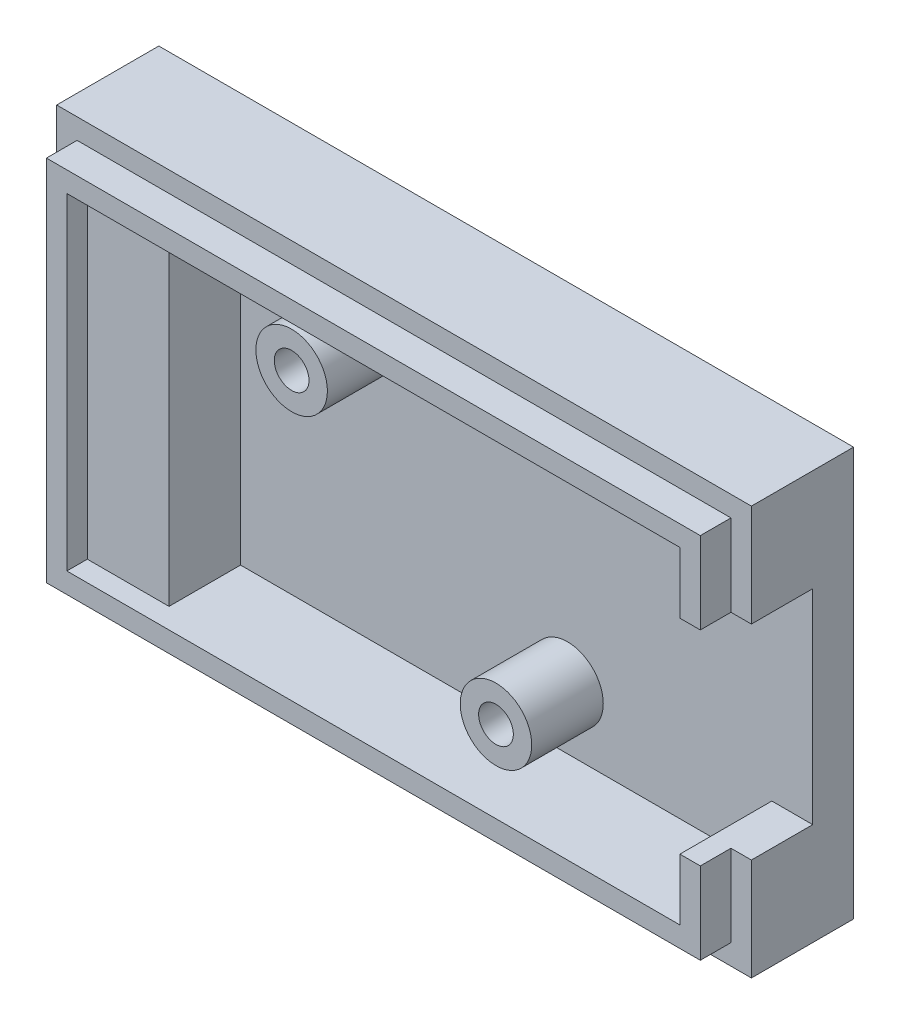
SolidWorks part; units mm, degrees
ref_plane "前视基准面" through (0, 0, 0) normal (0, 0, 1) x (1, 0, 0)
ref_plane "上视基准面" through (0, 0, 0) normal (0, 1, 0) x (1, 0, 0)
ref_plane "右视基准面" through (0, 0, 0) normal (1, 0, 0) x (0, 0, -1)
sketch "草图1" plane through (0, 0, 0) normal (0, 0, 1) x (1, 0, 0)
  line L1 (-17, 10) -> (17, 10)
  line L2 (-17, 10) -> (-17, -10)
  line L3 (-17, -10) -> (17, -10)
  line L4 (17, 10) -> (17, -10)
  line L5 (-17, 10) -> (17, -10) construction
  line L6 (-17, -10) -> (17, 10) construction
  point P0 (0, 0)
  dimension "D1" = 20
  dimension "D2" = 34
extrude "凸台-拉伸1" add sketch "草图1" along normal blind 6.5
sketch "草图2" plane through (0, 0, 6.5) normal (0, 0, 1) x (1, 0, 0)
  line L0 (17, -10) -> (17, 10) construction
  line L1 (-15, 8) -> (15, 8)
  line L2 (-15, 8) -> (-15, -8)
  line L3 (-15, -8) -> (15, -8)
  line L4 (15, 8) -> (15, -8)
  line L5 (-15, 8) -> (15, -8) construction
  line L6 (-15, -8) -> (15, 8) construction
  line L7 (17, 10) -> (-17, 10) construction
  point P0 (0, 0)
  dimension "D1" = 2
  dimension "D2" = 2
extrude "切除-拉伸1" cut sketch "草图2" against normal blind 4.5
sketch "草图3" plane through (17, 0, 0) normal (1, 0, 0) x (0, 0, -1)
  line L0 (-6.5, -10) -> (-6.5, 10) construction
  line L1 (-6.5, 5) -> (-2, 5)
  line L2 (-6.5, 5) -> (-6.5, -5)
  line L3 (-6.5, -5) -> (-2, -5)
  line L4 (-2, 5) -> (-2, -5)
  line L5 (-6.5, 10) -> (0, 10) construction
  line L6 (-6.5, -10) -> (0, -10) construction
  dimension "D1" = 5
  dimension "D2" = 5
  dimension "D3" = 4.5
extrude "切除-拉伸2" cut sketch "草图3" against normal blind 2
sketch "草图4" plane through (0, 0, 6.5) normal (0, 0, 1) x (1, 0, 0)
  line L0 (16, 5) -> (16, 9)
  line L1 (15, 5) -> (17, 5) construction
  line L2 (16, 9) -> (-16, 9)
  line L3 (-16, 9) -> (-16, -9)
  line L4 (-16, -9) -> (16, -9)
  line L5 (16, -9) -> (16, -5)
  line L6 (15, -5) -> (17, -5) construction
  line L7 (16, -5) -> (17, -5)
  line L8 (17, -5) -> (17, -10)
  line L9 (17, -10) -> (-17, -10)
  line L10 (-17, -10) -> (-17, 10)
  line L11 (-17, 10) -> (17, 10)
  line L12 (17, 10) -> (17, 5)
  line L13 (17, 5) -> (16, 5)
  dimension "D1" = 1
  dimension "D2" = 1
  dimension "D3" = 1
extrude "切除-拉伸3" cut sketch "草图4" against normal blind 1.5
sketch "草图5" plane through (0, 0, 2) normal (0, 0, 1) x (1, 0, 0)
  line L0 (-15, -8) -> (15, -8) construction
  line L1 (-15, 8) -> (-11, 8)
  line L2 (-15, 8) -> (-15, -8)
  line L3 (-15, -8) -> (-11, -8)
  line L4 (-11, 8) -> (-11, -8)
  dimension "D1" = 4
extrude "凸台-拉伸2" add sketch "草图5" along normal blind 3.5
sketch "草图6" plane through (0, 0, 2) normal (0, 0, 1) x (1, 0, 0)
  line L0 (-15, 8) -> (-15, -8) construction
  line L2 (15, 8) -> (-11, 8) construction
  line L3 (-15, -8) -> (15, -8) construction
  line L4 (15, -8) -> (15, -5) construction
  circle A0 centre (-5, 5) radius 1.75
  circle A1 centre (5, -5) radius 1.75
  dimension "D1" = 3.5
  dimension "D2" = 3.5
  dimension "D6" = 3
  dimension "D3" = 10
  dimension "D4" = 10
  dimension "D5" = 3
extrude "凸台-拉伸3" add sketch "草图6" along normal blind 3.5
sketch "草图7" plane through (0, 0, 5.5) normal (0, 0, 1) x (1, 0, 0)
  circle A0 centre (-5, 5) radius 0.85
  circle A1 centre (5, -5) radius 0.85
  dimension "D1" = 1.7
  dimension "D2" = 1.7
extrude "切除-拉伸4" cut sketch "草图7" against normal through all
sketch "草图8" plane through (0, 0, 0) normal (0, 0, -1) x (-1, 0, 0)
  circle A0 centre (-5, -5) radius 1.5
  circle A1 centre (5, 5) radius 1.5
  dimension "D1" = 3
  dimension "D2" = 3
extrude "切除-拉伸5" cut sketch "草图8" against normal blind 1
